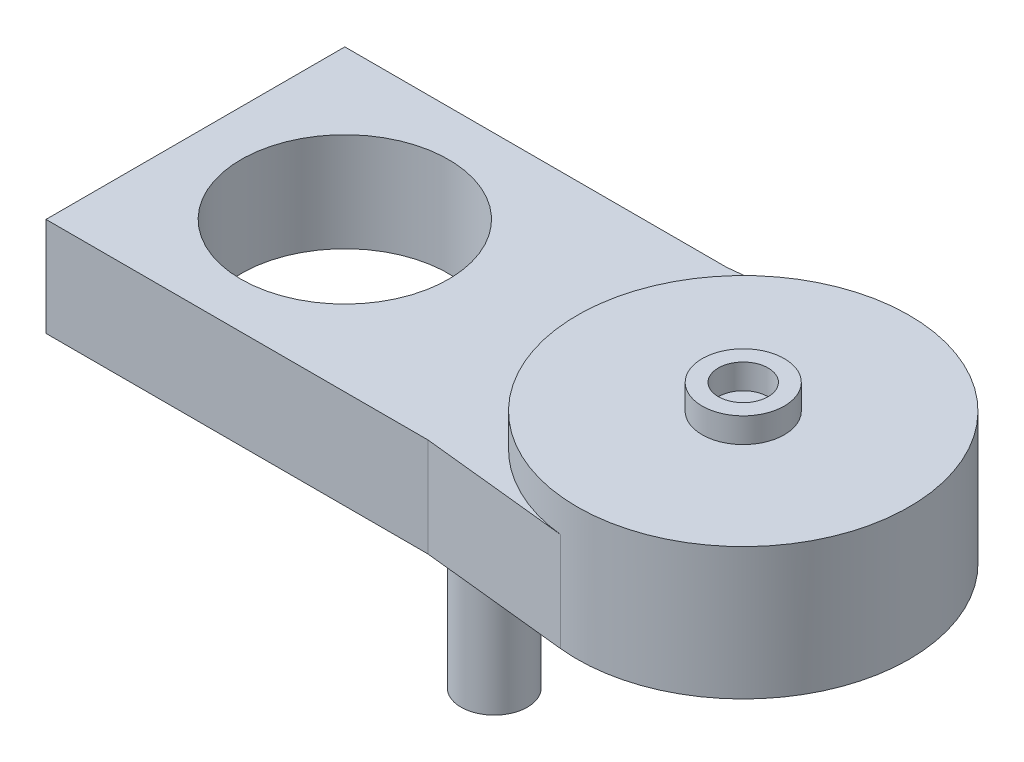
SolidWorks part; units mm, degrees
ref_plane "Front Plane" through (0, 0, 0) normal (0, 0, 1) x (1, 0, 0)
ref_plane "Top Plane" through (0, 0, 0) normal (0, 1, 0) x (1, 0, 0)
ref_plane "Right Plane" through (0, 0, 0) normal (1, 0, 0) x (0, 0, -1)
sketch "Sketch1" plane through (0, 0, 0) normal (0, 1, 0) x (1, 0, 0)
  line L0 (-36.0976, 0) -> (47.5883, 0) construction
  line L1 (14, 9) -> (22.9503, 9.9448)
  line L2 (-9, -9) -> (9, -9)
  line L3 (-9, -9) -> (-9, 9)
  line L4 (-9, 9) -> (9, 9)
  line L6 (-9, -9) -> (9, 9) construction
  line L7 (-9, 9) -> (9, -9) construction
  line L8 (9, -9) -> (14, -9)
  line L10 (9, 9) -> (14, 9)
  line L12 (9, -9) -> (14, 9) construction
  line L13 (9, 9) -> (14, -9) construction
  line L14 (14, -9) -> (22.9503, -9.9448)
  circle A0 centre (0, 0) radius 6.25
  arc A1 (22.9503, -9.9448) -> (22.9503, 9.9448) centre (24, 0) ccw
  point P3 (0, 0)
  point P10 (11.5, 0)
  point P13 (0, 0)
  dimension "D3" = 12.5
  dimension "D6" = 20
  dimension "D1" = 18
  dimension "D2" = 18
  dimension "D4" = 5
  dimension "D5" = 18
extrude "Boss-Extrude2" add sketch "Sketch1" along normal blind 5.95
sketch "Sketch3" plane through (0, 5.95, 0) normal (0, 1, 0) x (1, 0, 0)
  line L0 (-10.9363, 0) -> (39.1113, 0) construction
  circle A0 centre (24, 0) radius 10
  arc A1 (22.9503, -9.9448) -> (22.9503, 9.9448) centre (24, 0) ccw construction
  dimension "D1" = 20
extrude "Boss-Extrude3" add sketch "Sketch3" along normal blind 2
sketch "Sketch4" plane through (0, 0, 0) normal (0, -1, 0) x (1, 0, 0)
  line L0 (9, 9) -> (9, -9) construction
  line L1 (-9, 9) -> (14, 9) construction
  line L2 (14, -9) -> (-9, -9) construction
  line L3 (14, 9) -> (14, -9) construction
  line L4 (13, 9) -> (13, -9) construction
  line L5 (-10.2489, 0) -> (36.2964, 0) construction
  circle A0 centre (13, 4) radius 2
  circle A1 centre (13, -4) radius 2
  dimension "D3" = 4
  dimension "D1" = 18
  dimension "D2" = 4
  dimension "D4" = 5
extrude "Boss-Extrude4" add sketch "Sketch4" along normal blind 10
sketch "Sketch5" plane through (0, 7.95, 0) normal (0, 1, 0) x (1, 0, 0)
  line L0 (-11.9183, 0) -> (37.2129, 0) construction
  line L1 (24, 10) -> (24, -10) construction
  circle A0 centre (24, 0) radius 10 construction
  circle A1 centre (24, 0) radius 1.5
  circle A2 centre (24, 0) radius 2.475
  dimension "D1" = 3
  dimension "D2" = 4.95
extrude "Boss-Extrude5" add sketch "Sketch5" along normal blind 1.5
